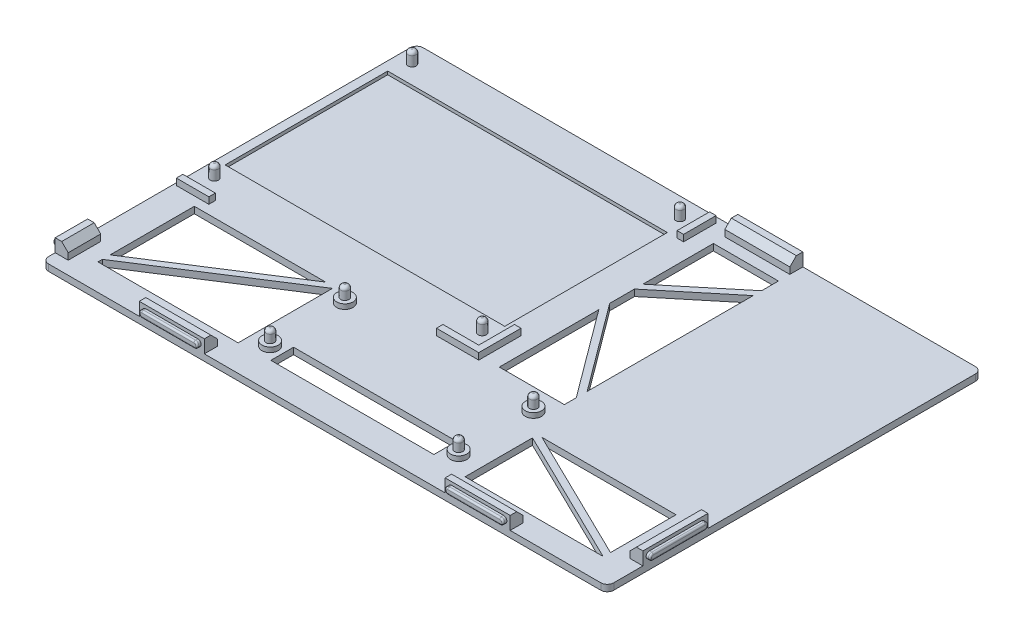
SolidWorks part; units mm, degrees
ref_plane "前基準面" through (0, 0, 0) normal (0, 0, 1) x (1, 0, 0)
ref_plane "上基準面" through (0, 0, 0) normal (0, 1, 0) x (1, 0, 0)
ref_plane "右基準面" through (0, 0, 0) normal (1, 0, 0) x (0, 0, -1)
sketch "草圖1" plane through (0, 0, 0) normal (0, 1, 0) x (1, 0, 0)
  line L0 (0, 57.6) -> (0, -57.6) construction
  line L1 (-86.9, 57.6) -> (86.9, 57.6)
  line L2 (-86.9, 57.6) -> (-86.9, -57.6)
  line L3 (-86.9, -57.6) -> (86.9, -57.6)
  line L4 (86.9, 57.6) -> (86.9, -57.6)
  line L5 (-86.9, 57.6) -> (86.9, -57.6) construction
  line L6 (-86.9, -57.6) -> (86.9, 57.6) construction
  line L7 (-86.9, 0) -> (86.9, 0) construction
  point P0 (0, 0)
  dimension "D1" = 173.8
  dimension "D2" = 115.2
extrude "填料-伸長1" add sketch "草圖1" along normal blind 2
sketch "草圖2" plane through (0, 2, 0) normal (0, 1, 0) x (1, 0, 0)
  line L0 (-86.9, 57.6) -> (-86.9, -57.6) construction
  line L1 (-86.16, 55.93) -> (3.84, 55.93)
  line L2 (-86.16, 55.93) -> (-86.16, -14.07)
  line L3 (-86.16, -14.07) -> (3.84, -14.07)
  line L4 (3.84, 55.93) -> (3.84, -14.07)
  line L5 (-86.16, 55.93) -> (3.84, -14.07) construction
  line L6 (-86.16, -14.07) -> (3.84, 55.93) construction
  line L7 (86.9, 57.6) -> (-86.9, 57.6) construction
  line L8 (-41.16, 55.93) -> (-41.16, -14.07) construction
  line L9 (-86.16, 20.93) -> (3.84, 20.93) construction
  point P0 (-41.16, 20.93)
  dimension "D1" = 90
  dimension "D2" = 70
  dimension "D3" = 0.74
  dimension "D4" = 1.67
sketch "草圖3" plane through (0, 2, 0) normal (0, 1, 0) x (1, 0, 0)
  line L0 (3.84, 55.93) -> (3.84, -14.07) construction
  line L1 (4.84, 55.93) -> (6.84, 55.93)
  line L2 (4.84, 55.93) -> (4.84, 45.93)
  line L3 (4.84, 45.93) -> (6.84, 45.93)
  line L4 (6.84, 55.93) -> (6.84, 45.93)
  line L5 (-86.16, -14.07) -> (3.84, -14.07) construction
  line L7 (4.84, -14.07) -> (4.84, -4.07)
  line L8 (4.84, -4.07) -> (6.84, -4.07)
  line L9 (6.84, -14.07) -> (6.84, -4.07)
  line L10 (6.84, -17.07) -> (-6.16, -17.07)
  line L11 (6.84, -17.07) -> (6.84, -15.07)
  line L12 (4.84, -15.07) -> (-6.16, -15.07)
  line L13 (-6.16, -17.07) -> (-6.16, -15.07)
  line L14 (3.84, -15.07) -> (3.84, -17.07) construction
  line L15 (4.84, -14.07) -> (4.84, -15.07)
  line L16 (6.84, -14.07) -> (6.84, -15.07)
  line L18 (-86.16, -17.07) -> (-76.16, -17.07)
  line L19 (-86.16, -17.07) -> (-86.16, -15.07)
  line L20 (-86.16, -15.07) -> (-76.16, -15.07)
  line L21 (-76.16, -17.07) -> (-76.16, -15.07)
  point P25 (0, 0)
  dimension "D1" = 2
  dimension "D2" = 10
  dimension "D3" = 1
  dimension "D4" = 2
  dimension "D5" = 2
  dimension "D6" = 2
  dimension "D7" = 1
  dimension "D8" = 1
  dimension "D9" = 10
  dimension "D10" = 1
  dimension "D11" = 10
extrude "填料-伸長2" add sketch "草圖3" along normal blind 2
sketch "草圖4" plane through (0, 2, 0) normal (0, 1, 0) x (1, 0, 0)
  line L1 (-86.16, 55.93) -> (3.84, 55.93) construction
  line L2 (3.84, 55.93) -> (3.84, -14.07) construction
  line L3 (-86.16, -14.07) -> (3.84, -14.07) construction
  line L4 (-41.16, 55.93) -> (-41.16, -14.07) construction
  circle A0 centre (0.04, 51.63) radius 1.25
  circle A1 centre (0.04, -9.17) radius 1.25
  circle A2 centre (-82.36, -9.17) radius 1.25
  circle A3 centre (-82.36, 51.63) radius 1.25
  dimension "D1" = 2.5
  dimension "D2" = 3.8
  dimension "D3" = 4.3
  dimension "D4" = 4.9
extrude "填料-伸長3" add sketch "草圖4" along normal blind 4
fillet "圓角2" radius 1 4 edges at (-82.36, 6, -52.88) (-82.36, 6, 7.92) (0.04, 6, 10.42) (0.04, 6, -50.38)
sketch "草圖5" plane through (0, 2, 0) normal (0, 1, 0) x (1, 0, 0)
  line L0 (-86.16, 55.93) -> (3.84, -14.07) construction
  line L1 (-84.16, 45.93) -> (1.84, 45.93)
  line L2 (-84.16, 45.93) -> (-84.16, -4.07)
  line L3 (-84.16, -4.07) -> (1.84, -4.07)
  line L4 (1.84, 45.93) -> (1.84, -4.07)
  line L5 (-84.16, 45.93) -> (1.84, -4.07) construction
  line L6 (-84.16, -4.07) -> (1.84, 45.93) construction
  line L7 (-86.16, 55.93) -> (3.84, 55.93) construction
  line L8 (-86.16, 55.93) -> (-86.16, -14.07) construction
  point P0 (-41.16, 20.93)
  dimension "D1" = 10
  dimension "D2" = 2
extrude "除料-伸長1" cut sketch "草圖5" against normal blind 1
sketch "草圖6" plane through (0, 2, 0) normal (0, 1, 0) x (1, 0, 0)
  line L1 (35.1797, 56.0179) -> (85.1797, 56.0179)
  line L2 (35.1797, 56.0179) -> (35.1797, -24.9821)
  line L3 (35.1797, -24.9821) -> (85.1797, -24.9821)
  line L4 (85.1797, 56.0179) -> (85.1797, -24.9821)
  line L5 (35.1797, 56.0179) -> (85.1797, -24.9821) construction
  line L6 (35.1797, -24.9821) -> (85.1797, 56.0179) construction
  point P0 (60.1797, 15.5179)
  point P5 (58.7637, 14.0537)
  point P6 (59.4717, 15.1639)
  point P7 (60.1797, 15.5179)
  dimension "D1" = 81
  dimension "D2" = 50
sketch "草圖7" plane through (0, 2, 0) normal (0, 1, 0) x (1, 0, 0)
  line L0 (0, 57.6) -> (0, -57.6) construction
  line L1 (-32.5, -18.9) -> (32.5, -18.9)
  line L2 (-32.5, -18.9) -> (-32.5, -49.1)
  line L3 (-32.5, -49.1) -> (32.5, -49.1)
  line L4 (32.5, -18.9) -> (32.5, -49.1)
  line L5 (-32.5, -18.9) -> (32.5, -49.1) construction
  line L6 (-32.5, -49.1) -> (32.5, -18.9) construction
  line L7 (-86.9, -57.6) -> (86.9, -57.6) construction
  point P0 (0, -34)
  point P5 (32.5, -34)
  point P6 (0, 0)
  point P7 (0, 0)
  point P10 (0, -35.7681)
  dimension "D1" = 65
  dimension "D2" = 30.2
  dimension "D3" = 8.5
sketch "草圖8" plane through (0, 2, 0) normal (0, 1, 0) x (1, 0, 0)
  line L0 (-32.5, -18.9) -> (32.5, -18.9) construction
  line L1 (32.5, -18.9) -> (32.5, -49.1) construction
  line L2 (-32.5, -49.1) -> (32.5, -49.1) construction
  line L3 (0, -18.9) -> (0, -49.1) construction
  circle A0 centre (29, -22.4) radius 2.5
  circle A1 centre (29, -22.4) radius 1.25
  circle A2 centre (29, -45.4) radius 2.5
  circle A3 centre (29, -45.4) radius 1.25
  circle A4 centre (-29, -45.4) radius 1.25
  circle A5 centre (-29, -45.4) radius 2.5
  circle A6 centre (-29, -22.4) radius 1.25
  circle A7 centre (-29, -22.4) radius 2.5
  dimension "D1" = 5
  dimension "D4" = 2.5
  dimension "D2" = 3.5
  dimension "D3" = 3.5
  dimension "D5" = 3.7
extrude "填料-伸長4" add sketch "草圖8" along normal blind 1.5 contours A6 | A7 A6 | A5 A4 | A4 | A0 A1 | A1 | A2 A3 | A3 region at (26.5707, 2, 22.4) region at (29, 2, 22.4) region at (26.5707, 2, 45.4) region at (29, 2, 45.4) region at (-29, 2, 45.4) region at (-31.4293, 2, 45.4) region at (-29, 2, 22.4) region at (-31.4293, 2, 22.4)
extrude "填料-伸長5" add sketch "草圖8<3>" along normal blind 5 contours A6 | A4 | A3 | A1 region at (29, 2, 22.4) region at (29, 2, 45.4) region at (-29, 2, 45.4) region at (-29, 2, 22.4)
sketch "草圖8<3>" plane through (0, 2, 0) normal (0, 1, 0) x (1, 0, 0) same geometry as "草圖8"
fillet "圓角3" radius 1 4 edges at (-29, 7, 46.65) (29, 7, 46.65) (29, 7, 23.65) (-29, 7, 23.65)
sketch "草圖9" plane through (0, 2, 0) normal (0, 1, 0) x (1, 0, 0)
  line L0 (0, 57.6) -> (0, -57.6) construction
  line L1 (-25.0798, -42.1) -> (25.0798, -42.1)
  line L2 (-25.0798, -42.1) -> (-25.0798, -49.1)
  line L3 (-25.0798, -49.1) -> (25.0798, -49.1)
  line L4 (25.0798, -42.1) -> (25.0798, -49.1)
  line L5 (-25.0798, -42.1) -> (25.0798, -49.1) construction
  line L6 (-25.0798, -49.1) -> (25.0798, -42.1) construction
  line L7 (-32.5, -49.1) -> (32.5, -49.1) construction
  point P0 (0, -45.6)
  dimension "D1" = 7
extrude "除料-伸長2" cut sketch "草圖9" against normal blind 2
sketch "草圖10" plane through (0, 2, 0) normal (0, 1, 0) x (1, 0, 0)
  line L0 (-86.9, 57.6) -> (86.9, 57.6) construction
  line L1 (11.8547, 57.6) -> (31.8547, 57.6)
  line L2 (11.8547, 57.6) -> (11.8547, 53.6)
  line L3 (11.8547, 53.6) -> (31.8547, 53.6)
  line L4 (31.8547, 57.6) -> (31.8547, 53.6)
  line L5 (0, 57.6) -> (0, -57.6) construction
  line L10 (86.9, 57.6) -> (86.9, -57.6) construction
  line L11 (86.9, -26.638) -> (82.9, -26.638)
  line L12 (86.9, -26.638) -> (86.9, -46.638)
  line L13 (86.9, -46.638) -> (82.9, -46.638)
  line L14 (82.9, -26.638) -> (82.9, -46.638)
  line L15 (-86.9, -57.6) -> (86.9, -57.6) construction
  line L16 (37.0319, -57.6) -> (57.0319, -57.6)
  line L17 (37.0319, -57.6) -> (37.0319, -53.6)
  line L18 (37.0319, -53.6) -> (57.0319, -53.6)
  line L19 (57.0319, -57.6) -> (57.0319, -53.6)
  line L20 (-57.0319, -57.6) -> (-57.0319, -53.6)
  line L21 (-37.0319, -53.6) -> (-57.0319, -53.6)
  line L22 (-37.0319, -57.6) -> (-37.0319, -53.6)
  line L23 (-37.0319, -57.6) -> (-57.0319, -57.6)
  line L24 (-86.9, 57.6) -> (-86.9, -57.6) construction
  line L25 (-86.9, -53.6) -> (-82.9, -53.6)
  line L26 (-86.9, -53.6) -> (-86.9, -43.6)
  line L27 (-86.9, -43.6) -> (-82.9, -43.6)
  line L28 (-82.9, -53.6) -> (-82.9, -43.6)
  dimension "D1" = 4
  dimension "D2" = 20
  dimension "D3" = 4
  dimension "D4" = 10
  dimension "D5" = 20
  dimension "D6" = 4
  dimension "D7" = 20
  dimension "D8" = 4
extrude "填料-伸長6" add sketch "草圖10" along normal blind 4
sketch "草圖11" plane through (0, 2, 0) normal (0, 1, 0) x (1, 0, 0)
  line L0 (-77.8796, -45.7226) -> (-37.4971, -19.8239)
  line L1 (-77.8796, -49.4672) -> (-34.7645, -49.4672)
  line L2 (-77.8796, -49.4672) -> (-77.8796, -48.0986)
  line L3 (-77.8796, -19.8239) -> (-37.4971, -19.8239)
  line L4 (-34.7645, -49.4672) -> (-34.7645, -20.4474)
  line L5 (-77.8796, -48.0986) -> (-34.7645, -20.4474)
  line L6 (-77.8796, -45.7226) -> (-77.8796, -19.8239)
  line L7 (31.8547, 44.9175) -> (11.8547, 28.4103)
  line L8 (11.8547, 50.0907) -> (31.8547, 50.0907)
  line L9 (11.8547, 50.0907) -> (11.8547, 28.4103)
  line L10 (11.8547, -15.7529) -> (31.8547, -15.7529)
  line L11 (31.8547, 50.0907) -> (31.8547, 44.9175)
  line L13 (11.8547, 25.8171) -> (31.8547, 42.3243)
  line L14 (11.8547, 18.1985) -> (31.8547, -8.7367)
  line L15 (11.8547, 14.8436) -> (31.8547, -12.0916)
  line L16 (31.8547, 42.3243) -> (31.8547, -8.7367)
  line L17 (11.8547, 25.8171) -> (11.8547, 18.1985)
  line L18 (11.8547, 14.8436) -> (11.8547, -15.7529)
  line L19 (31.8547, -12.0916) -> (31.8547, -15.7529)
  line L20 (78.3594, -48.0628) -> (37.1158, -27.9151)
  line L21 (37.1158, -27.9151) -> (78.3594, -27.9151)
  line L22 (35.8042, -29.5002) -> (35.8042, -50.2291)
  line L23 (35.8042, -50.2291) -> (78.2374, -50.2291)
  line L24 (78.3594, -27.9151) -> (78.3594, -48.0628)
  line L25 (35.8042, -29.5002) -> (78.2374, -50.2291)
  point P29 (78.3594, -27.9151)
  dimension "D1" = 2
  dimension "D2" = 2
  dimension "D3" = 2
  dimension "D4" = 2
extrude "除料-伸長3" cut sketch "草圖11" against normal through all
fillet "圓角1" radius 2 4 edges at (86.9, 1, -57.6) (-86.9, 1, -57.6) (-86.9, 1, 57.6) (86.9, 1, 57.6)
chamfer "導角1" distance 2 angle 45 5 edges at (82.9, 6, 36.638) (47.0319, 6, 53.6) (-47.0319, 6, 53.6) (-82.9, 6, 48.6) (21.8547, 6, -53.6)
sketch "草圖13" plane through (86.9, 0, 0) normal (1, 0, 0) x (0, 0, -1)
  line L0 (-44.638, 4) -> (-28.638, 4) construction
  line L1 (-44.638, 5) -> (-28.638, 5)
  line L2 (-44.638, 3) -> (-28.638, 3)
  line L4 (-46.638, 4) -> (-26.638, 4) construction
  line L5 (-46.638, 6) -> (-46.638, 2) construction
  arc A0 (-44.638, 5) -> (-44.638, 3) centre (-44.638, 4) ccw
  arc A1 (-28.638, 3) -> (-28.638, 5) centre (-28.638, 4) ccw
  point P2 (-36.638, 4)
  point P7 (-35.1384, 6.7539)
  point P8 (0, 0)
  point P9 (-34.25, 4)
  point P15 (0, 0)
  point P16 (-36.638, 4)
  dimension "D1" = 2
  dimension "D2" = 16
extrude "填料-伸長8" add sketch "草圖13" along normal blind 1.2
sketch "草圖14" plane through (0, 0, -57.6) normal (0, 0, -1) x (-1, 0, 0)
  line L0 (-31.8547, 4) -> (-11.8547, 4) construction
  line L1 (-31.8547, 6) -> (-31.8547, 2) construction
  line L2 (-29.8547, 4) -> (-13.8547, 4) construction
  line L3 (-29.8547, 5) -> (-13.8547, 5)
  line L4 (-29.8547, 3) -> (-13.8547, 3)
  arc A0 (-29.8547, 5) -> (-29.8547, 3) centre (-29.8547, 4) ccw
  arc A1 (-13.8547, 3) -> (-13.8547, 5) centre (-13.8547, 4) ccw
  point P7 (-21.8547, 4)
  point P12 (0, 0)
  point P13 (-21.8547, 4)
  dimension "D1" = 16
  dimension "D2" = 2
extrude "填料-伸長9" add sketch "草圖14" along normal blind 1.2
sketch "草圖15" plane through (0, 0, 57.6) normal (0, 0, 1) x (1, 0, 0)
  line L0 (-57.0319, 4) -> (-37.0319, 4) construction
  line L1 (-57.0319, 6) -> (-57.0319, 2) construction
  line L2 (-37.0319, 6) -> (-37.0319, 2) construction
  line L3 (-55.0319, 4) -> (-39.0319, 4) construction
  line L4 (-55.0319, 5) -> (-39.0319, 5)
  line L5 (-55.0319, 3) -> (-39.0319, 3)
  line L6 (0, 2) -> (0, 0) construction
  line L7 (55.0319, 4) -> (39.0319, 4) construction
  line L8 (55.0319, 5) -> (39.0319, 5)
  line L9 (55.0319, 3) -> (39.0319, 3)
  arc A0 (-55.0319, 5) -> (-55.0319, 3) centre (-55.0319, 4) ccw
  arc A1 (-39.0319, 3) -> (-39.0319, 5) centre (-39.0319, 4) ccw
  arc A2 (55.0319, 5) -> (55.0319, 3) centre (55.0319, 4) cw
  arc A3 (39.0319, 3) -> (39.0319, 5) centre (39.0319, 4) cw
  point P8 (-47.0319, 4)
  point P16 (47.0319, 4)
  dimension "D1" = 16
  dimension "D2" = 2
extrude "填料-伸長11" add sketch "草圖15" along normal blind 1.2
sketch "草圖16" plane through (-86.9, 0, 0) normal (-1, 0, 0) x (0, 0, 1)
  line L0 (43.6, 4) -> (53.6, 4) construction
  line L1 (43.6, 6) -> (43.6, 2) construction
  line L2 (53.6, 6) -> (53.6, 2) construction
  line L3 (45.1, 4) -> (52.1, 4) construction
  line L4 (45.1, 5) -> (52.1, 5)
  line L5 (45.1, 3) -> (52.1, 3)
  arc A0 (45.1, 5) -> (45.1, 3) centre (45.1, 4) ccw
  arc A1 (52.1, 3) -> (52.1, 5) centre (52.1, 4) ccw
  point P8 (48.6, 4)
  point P13 (48.6, 4)
  dimension "D1" = 7
  dimension "D2" = 2
extrude "填料-伸長12" add sketch "草圖16" along normal blind 1.2
fillet "圓角4" radius 0.5 20 edges at (12.8547, 4, -58.8) (21.8547, 3, -58.8) (30.8547, 4, -58.8) (88.1, 4, 27.638) (88.1, 3, 36.638) (88.1, 4, 45.638) (56.0319, 4, 58.8) (47.0319, 3, 58.8) (38.0319, 4, 58.8) (-88.1, 4, 53.1) (-88.1, 3, 48.6) (-88.1, 4, 44.1) (-38.0319, 4, 58.8) (-47.0319, 3, 58.8) (-56.0319, 4, 58.8) (21.8547, 5, -58.8) (88.1, 5, 36.638) (47.0319, 5, 58.8) (-88.1, 5, 48.6) (-47.0319, 5, 58.8)
